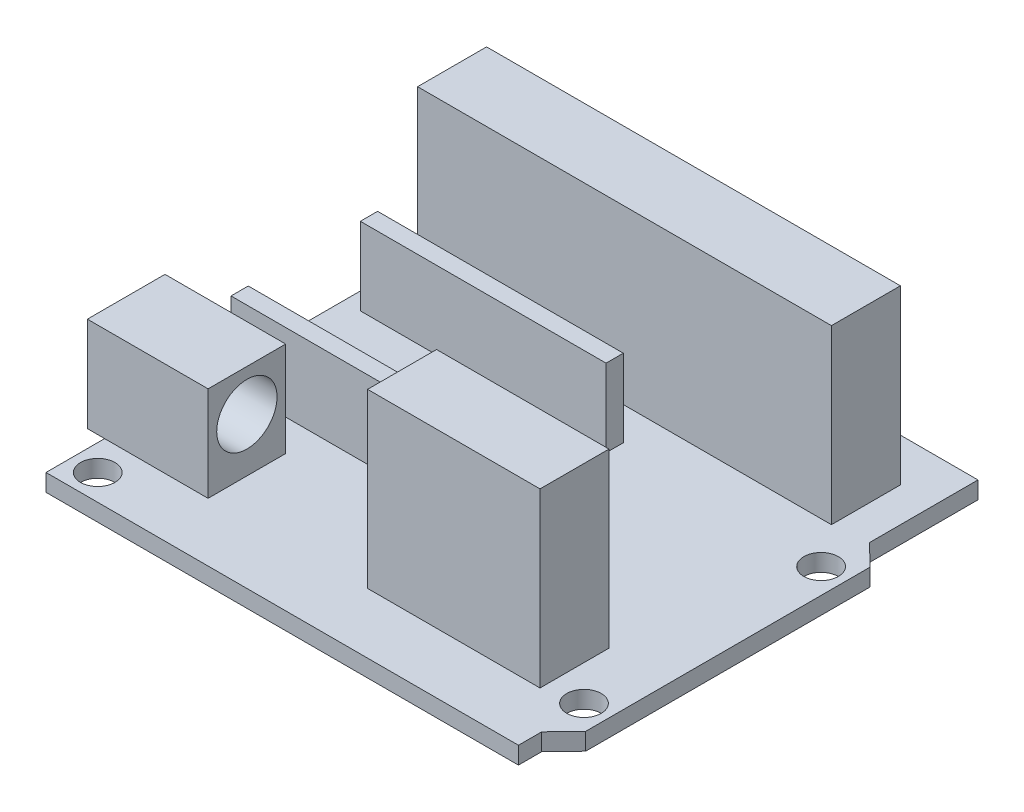
SolidWorks part; units mm, degrees
ref_plane "Front Plane" through (0, 0, 0) normal (0, 0, 1) x (1, 0, 0)
ref_plane "Top Plane" through (0, 0, 0) normal (0, 1, 0) x (1, 0, 0)
ref_plane "Right Plane" through (0, 0, 0) normal (1, 0, 0) x (0, 0, -1)
sketch "Sketch1" plane through (0, 0, 0) normal (0, 1, 0) x (1, 0, 0)
  line L0 (54.8, 53.3) -> (54.8, 40.7)
  line L1 (0, 0) -> (57.3, 0)
  line L2 (0, 0) -> (0, 53.3)
  line L3 (0, 53.3) -> (54.8, 53.3)
  line L4 (54.8, 40.7) -> (57.3, 38.3)
  line L5 (54.8, 0) -> (54.8, 2.6958)
  line L6 (0, 3) -> (3, 3) construction
  line L7 (3, 3) -> (3, 0) construction
  line L8 (54.8, 2.6958) -> (57.3, 5.3)
  line L9 (57.3, 5.3) -> (57.3, 0) construction
  line L10 (57.3, 38.3) -> (57.3, 5.3)
  line L11 (4, 53.3) -> (4, 50.8) construction
  line L12 (4, 50.8) -> (0, 50.8) construction
  line L13 (57.3, 8) -> (54.4, 8) construction
  line L14 (54.4, 8) -> (54.4, 10) construction
  line L15 (54.4, 8) -> (54.4, 0) construction
  line L16 (54.4, 35.5) -> (57.3, 35.5) construction
  line L17 (54.4, 35.5) -> (54.4, 53.3) construction
  circle A0 centre (3, 3) radius 2
  circle A1 centre (4, 50.8) radius 2
  circle A2 centre (54.4, 8) radius 2
  circle A3 centre (54.4, 35.5) radius 2
  point P19 (4, 50.8)
  point P20 (3, 3)
  point P30 (54.4, 35.5)
  point P31 (54.4, 8)
  dimension "D5" = 4
  dimension "D7" = 4
  dimension "D10" = 4
  dimension "D14" = 4
  dimension "D1" = 53.3
  dimension "D2" = 57.3
  dimension "D3" = 12.6
  dimension "D4" = 54.8
  dimension "D6" = 3
  dimension "D8" = 2.5
  dimension "D9" = 4
  dimension "D11" = 2.9
  dimension "D12" = 8
  dimension "D13" = 33
  dimension "D15" = 2.9
  dimension "D16" = 17.8
extrude "Boss-Extrude1" add sketch "Sketch1" along normal blind 2 contours L10 L4 L0 L3 L2 L1 L5 L8 A0 region at (28.2321, 0, -26.5425)
sketch "Sketch2" plane through (0, 2, 0) normal (0, 1, 0) x (1, 0, 0)
  line L0 (0, 34.4602) -> (2, 34.4602) construction
  line L1 (2, 36.4602) -> (30.5, 36.4602)
  line L2 (2, 36.4602) -> (2, 34.4602)
  line L3 (2, 34.4602) -> (30.5, 34.4602)
  line L4 (30.5, 36.4602) -> (30.5, 34.4602)
  line L5 (0, 0) -> (0, 53.3) construction
  dimension "D1" = 28.5
  dimension "D2" = 2
  dimension "D3" = 2
extrude "Boss-Extrude2" add sketch "Sketch2" along normal blind 9
pattern_linear "LPattern1" count 2 spacing 15 along (0, 0, 1) of "Boss-Extrude2"
sketch "Sketch3" plane through (0, 2, 0) normal (0, 1, 0) x (1, 0, 0)
  line L0 (57.3, 7) -> (50.3, 7) construction
  line L1 (57.3, 38.3) -> (57.3, 5.3) construction
  line L2 (50.3, 7) -> (50.3, 0) construction
  line L3 (0, 0) -> (54.8, 0) construction
  line L5 (50.3, 7) -> (30.3, 7)
  line L6 (50.3, 7) -> (50.3, 15)
  line L7 (50.3, 15) -> (30.3, 15)
  line L8 (30.3, 7) -> (30.3, 15)
  dimension "D1" = 7
  dimension "D2" = 7
  dimension "D3" = 20
  dimension "D4" = 8
extrude "Boss-Extrude3" add sketch "Sketch3" along normal blind 20
sketch "Sketch4" plane through (0, 2, 0) normal (0, 1, 0) x (1, 0, 0)
  line L0 (50.8, 53.3) -> (50.8, 48.3) construction
  line L1 (0, 53.3) -> (54.8, 53.3) construction
  line L2 (50.8, 48.3) -> (54.8, 48.3) construction
  line L3 (54.8, 53.3) -> (54.8, 40.7) construction
  line L5 (50.8, 48.3) -> (2.8, 48.3)
  line L6 (50.8, 48.3) -> (50.8, 40.3)
  line L7 (50.8, 40.3) -> (2.8, 40.3)
  line L8 (2.8, 48.3) -> (2.8, 40.3)
  dimension "D1" = 5
  dimension "D2" = 4
  dimension "D3" = 48
  dimension "D4" = 8
extrude "Boss-Extrude4" add sketch "Sketch4" along normal blind 20
ref_plane "Plane1" through (-2, 0, 0) normal (-1, 0, 0) x (0, 0, 1)
sketch "Sketch5" plane through (-2, 0, 0) normal (-1, 0, 0) x (0, 0, 1)
  line L0 (0, 2) -> (-53.3, 2) construction
  line L1 (-6.8, 2) -> (-15.8, 2)
  line L2 (-6.8, 2) -> (-6.8, 13)
  line L3 (-6.8, 13) -> (-15.8, 13)
  line L4 (-15.8, 2) -> (-15.8, 13)
  line L5 (0, 2) -> (-6.8, 2) construction
  line L6 (-11.3, 13) -> (-11.3, 8.2) construction
  circle A0 centre (-11.3, 8.2) radius 3.5
  dimension "D5" = 7
  dimension "D1" = 6.8
  dimension "D2" = 9
  dimension "D3" = 11
  dimension "D4" = 4.8
extrude "Boss-Extrude5" add sketch "Sketch5" against normal blind 14
sketch "Sketch6" plane through (0, 0, 0) normal (0, -1, 0) x (1, 0, 0)
  circle A0 centre (6.4883, -7.768) radius 0.5
  dimension "D1" = 1
extrude "Boss-Extrude6" add sketch "Sketch6" along normal blind 2.2
sketch "Sketch7" plane through (0, 0, 0) normal (0, -1, 0) x (1, 0, 0)
  line L0 (6.4883, -7.768) -> (11.8863, -9.8733)
pattern_linear "LPattern2" count 2 spacing 5 along (0.9317, 0, -0.3634) of "Boss-Extrude6"
pattern_linear "LPattern3" count 2 spacing 5 along (0, 0, -1) of "Boss-Extrude6"
